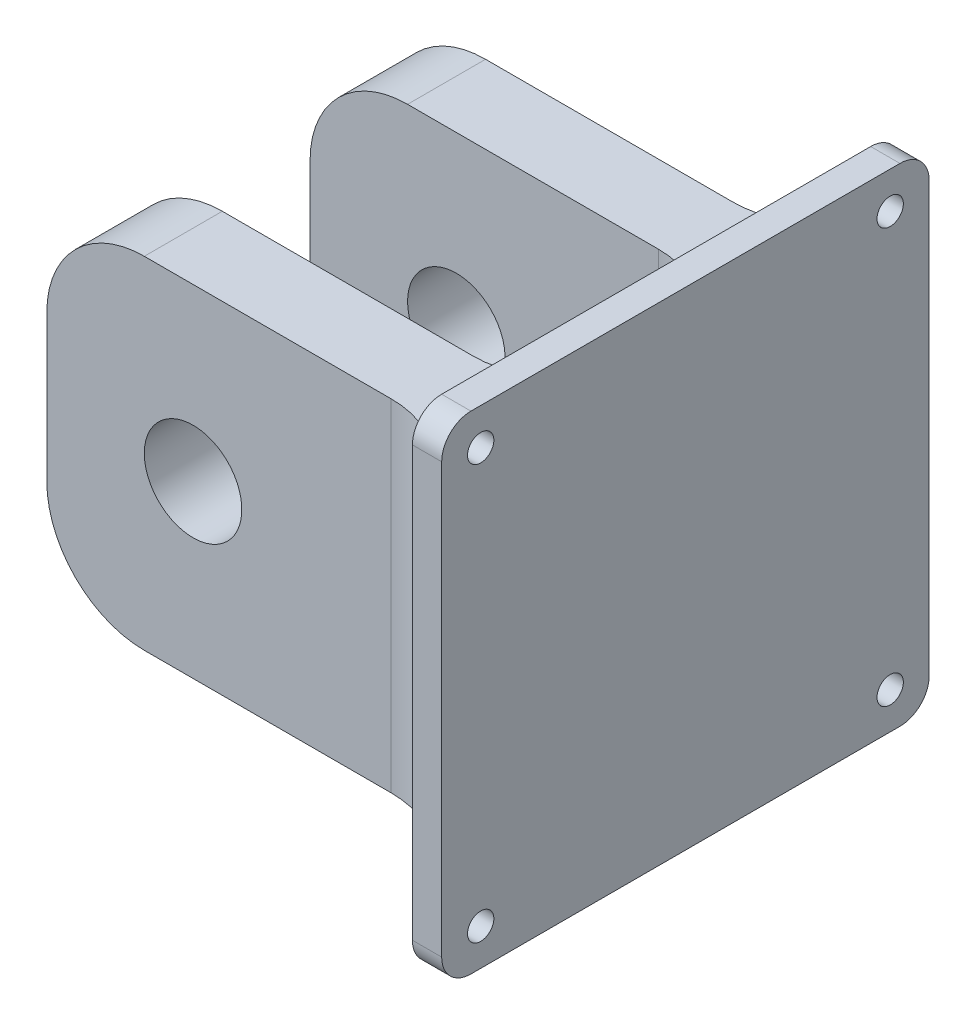
SolidWorks part; units mm, degrees
ref_plane "Plan de face" through (0, 0, 0) normal (0, 0, 1) x (1, 0, 0)
ref_plane "Plan de dessus" through (0, 0, 0) normal (0, 1, 0) x (1, 0, 0)
ref_plane "Plan de droite" through (0, 0, 0) normal (1, 0, 0) x (0, 0, -1)
sketch "Esquisse3" plane through (0, 0, 0) normal (1, 0, 0) x (0, 0, -1)
  line L1 (-25, -25) -> (25, -25)
  line L2 (-25, -25) -> (-25, 25)
  line L3 (-25, 25) -> (25, 25)
  line L4 (25, -25) -> (25, 25)
  line L5 (-25, -25) -> (25, 25) construction
  line L6 (-25, 25) -> (25, -25) construction
  point P0 (0, 0)
  dimension "D1" = 50
  dimension "D2" = 50
sketch "Esquisse4" plane through (0, 0, 0) normal (1, 0, 0) x (0, 0, -1)
  line L1 (-17.5, -17.5) -> (17.5, -17.5)
  line L2 (-17.5, -17.5) -> (-17.5, 17.5)
  line L3 (-17.5, 17.5) -> (17.5, 17.5)
  line L4 (17.5, -17.5) -> (17.5, 17.5)
  line L5 (-17.5, -17.5) -> (17.5, 17.5) construction
  line L6 (-17.5, 17.5) -> (17.5, -17.5) construction
  line L7 (17.5, -17.5) -> (9.5, -17.5)
  line L8 (17.5, -17.5) -> (17.5, 17.5)
  line L9 (17.5, 17.5) -> (9.5, 17.5)
  line L10 (9.5, -17.5) -> (9.5, 17.5)
  line L11 (-9.5, 17.5) -> (-17.5, 17.5)
  line L12 (-9.5, 17.5) -> (-9.5, -17.5)
  line L13 (-9.5, -17.5) -> (-17.5, -17.5)
  line L14 (-17.5, 17.5) -> (-17.5, -17.5)
  point P0 (0, 0)
  dimension "D1" = 35
  dimension "D2" = 35
  dimension "D3" = 8
  dimension "D4" = 8
extrude "Boss.-Extru.3" add sketch "Esquisse3" along normal blind 3
extrude "Boss.-Extru.5" add sketch "Esquisse4" against normal blind 45 contours L11 L2 L13 L12 | L7 L10 L9 L4
sketch "Esquisse7" plane through (0, 0, -17.5) normal (0, 0, -1) x (-1, 0, 0)
  line L0 (0, -17.5) -> (0, 17.5) construction
  circle A0 centre (30, 0) radius 5
  dimension "D1" = 30
extrude "Enlèv. mat.-Extru.1" cut sketch "Esquisse7" against normal blind 40 contours A0
fillet "Congé1" radius 10 6 edges at (0, 0, -17.5) (0, 0, 17.5) (-45, 17.5, 13.5) (-45, -17.5, 13.5) (-45, -17.5, -13.5) (-45, 17.5, -13.5)
fillet "Congé2" radius 9.25 2 edges at (0, 0, -9.5) (0, 0, 9.5)
fillet "Congé3" radius 3 4 edges at (1.5, -25, 25) (1.5, 25, 25) (1.5, 25, -25) (1.5, -25, -25)
sketch "Esquisse8" plane through (0, 0, 0) normal (-1, 0, 0) x (0, 0, 1)
  line L1 (-21, 21.25) -> (21, 21.25)
  line L2 (-21, 21.25) -> (-21, -21.25)
  line L3 (-21, -21.25) -> (21, -21.25)
  line L4 (21, 21.25) -> (21, -21.25)
  line L5 (-21, 21.25) -> (21, -21.25) construction
  line L6 (-21, -21.25) -> (21, 21.25) construction
  point P0 (0, 0)
  dimension "D1" = 42.5
  dimension "D2" = 42
hole_wizard "Dégagement M2.51" positions "Esquisse11" profile "Esquisse12" hole size "M2.5" standard "AS" end condition up to next
sketch "Esquisse11" plane through (0, 0, 0) normal (-1, 0, 0) x (0, 0, 1)
  point P0 (21, 21.25)
  point P3 (-21, 21.25)
  point P6 (-21, -21.25)
  point P9 (21, -21.25)
sketch "Esquisse12" plane through (0, 21.25, 21) normal (0, 1, 0) x (0, 0, 1)
  line L0 (0, 0) -> (0, 3)
  line L1 (0, 3) -> (1.35, 3)
  line L2 (1.35, 3) -> (1.35, 0)
  line L5 (1.35, 0) -> (0, 0)
  line L11 (0, -6.35) -> (0, 107.95) construction
  dimension "Diamètre du perçage jusqu'au prochain" = 2.7
  dimension "Profondeur du perçage jusqu'au prochain" = 3
